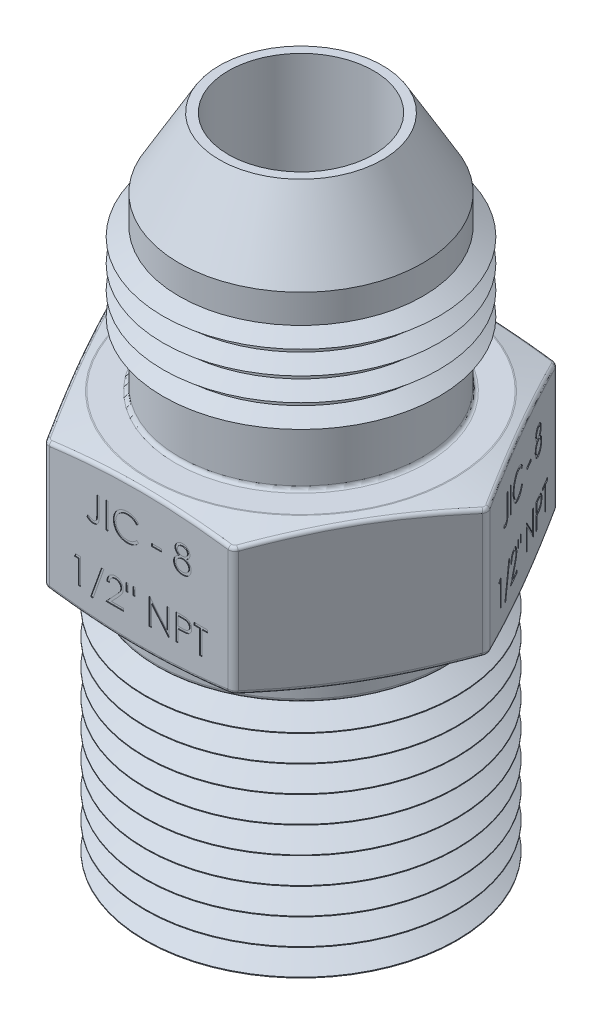
SolidWorks part; units mm, degrees
other "Fitting Body"
material "Plain Carbon Steel"
ref_plane "Front Plane" through (0, 0, 0) normal (0, 0, 1) x (1, 0, 0)
ref_plane "Top Plane" through (0, 0, 0) normal (0, 1, 0) x (1, 0, 0)
ref_plane "Right Plane" through (0, 0, 0) normal (1, 0, 0) x (0, 0, -1)
sketch "Sketch1" plane through (0, 0, 0) normal (0, 1, 0) x (1, 0, 0)
  line L1 (12.8316, 0) -> (6.4158, 11.1125)
  line L2 (6.4158, 11.1125) -> (-6.4158, 11.1125)
  line L3 (-6.4158, 11.1125) -> (-12.8316, 0)
  line L4 (-12.8316, 0) -> (-6.4158, -11.1125)
  line L5 (-6.4158, -11.1125) -> (6.4158, -11.1125)
  line L6 (6.4158, -11.1125) -> (12.8316, 0)
  circle A0 centre (0, 0) radius 11.1125 construction
  dimension "D1" = 22.225
extrude "Boss-Extrude1" add sketch "Sketch1" along normal mid plane 9.906
sketch "Sketch2" plane through (0, 4.953, 0) normal (0, 1, 0) x (1, 0, 0)
  circle A0 centre (0, 0) radius 10.414
  dimension "D1" = 20.828
extrude "Cut-Extrude1" cut sketch "Sketch2" against normal blind 8.255 draft 75 flip side to cut
sketch "Sketch3" plane through (0, -4.953, 0) normal (0, -1, 0) x (1, 0, 0)
  circle A0 centre (0, 0) radius 10.414 construction
  circle A1 centre (0, 0) radius 10.414
extrude "Cut-Extrude2" cut sketch "Sketch3" against normal blind 8.255 draft 75 flip side to cut
fillet "Fillet1" radius 0.508 6 edges at (6.4158, 0, 11.1125) (-6.4158, 0, 11.1125) (-12.8316, 0, 0) (-6.4158, 0, -11.1125) (6.4158, 0, -11.1125) (12.8316, 0, 0)
fillet "Fillet2" radius 0.254 25 edges at (12.7485, -4.3274, 0.0679) (6.433, -4.3274, -11.0066) (-6.3155, -4.3274, -11.0744) (-12.7485, -4.3274, -0.0679) (-6.433, -4.3274, 11.0066) (6.3155, -4.3274, 11.0744) (-6.3155, 4.3274, 11.0744) (-12.7485, 4.3274, 0.0679) (-6.433, 4.3274, -11.0066) (6.3155, 4.3274, -11.0744) (12.7485, 4.3274, -0.0679) (6.433, 4.3274, 11.0066) (0, 4.953, 10.414)
sketch "Sketch8" plane through (0, 4.953, 0) normal (0, 1, 0) x (1, 0, 0)
  circle A0 centre (0, 0) radius 8.3439
  dimension "D1" = 16.6878
extrude "Boss-Extrude6" add sketch "Sketch8" along normal blind 16.51
fillet "Fillet3" radius 0.254 1 edges at (0, 4.953, 8.3439)
chamfer "Chamfer1" distance 4.7625 angle 30 1 edges at (0, 21.463, 8.3439) first distance on face at (0, 5.207, 8.3439)
sketch "Sketch12" plane through (0, 0, 0) normal (0, 0, 1) x (1, 0, 0)
  line L0 (0, 0) -> (0, 14.097) construction
  line L1 (0, 14.097) -> (0, 21.463) construction
  line L2 (5.5943, 21.463) -> (-5.5943, 21.463) construction
  line L3 (0, 14.097) -> (8.3439, 14.097) construction
  line L4 (8.3439, 5.207) -> (8.3439, 16.7005) construction
  line L5 (8.3439, 14.097) -> (9.4438, 14.097) construction
  line L6 (8.3439, 14.732) -> (8.3439, 13.462)
  line L7 (8.3439, 14.732) -> (9.4438, 14.097)
  line L8 (9.4438, 14.097) -> (8.3439, 13.462)
  dimension "D1" = 60
  dimension "D2" = 1.27
  dimension "D3" = 7.366
revolve "Revolve2" add sketch "Sketch12" angle 360 about L0
pattern_linear "LPattern2" count 4 spacing 1.5875 along (0, -1, 0) of "Revolve2"
sketch "Sketch4" plane through (0, -4.953, 0) normal (0, -1, 0) x (1, 0, 0)
  circle A0 centre (0, 0) radius 9.906
  dimension "D1" = 19.812
extrude "Boss-Extrude7" add sketch "Sketch4" along normal blind 2.032
sketch "Sketch13" plane through (0, -6.985, 0) normal (0, -1, 0) x (1, 0, 0)
  circle A0 centre (0, 0) radius 10.668
  dimension "D1" = 21.336
extrude "Boss-Extrude8" add sketch "Sketch13" along normal offset from surface (16.256 mm away) 44.704 up to face at (0, 21.463, 5.5943)
sketch "Sketch14" plane through (0, 0, 0) normal (0, 0, 1) x (1, 0, 0)
  line L0 (0, 0) -> (0, -23.241) construction
  line L1 (-10.668, -23.241) -> (10.668, -23.241) construction
  line L2 (0, -23.241) -> (9.144, -23.241) construction
  line L3 (9.144, -23.241) -> (10.7152, -23.241) construction
  line L4 (10.7152, -23.241) -> (12.5295, -23.241) construction
  line L5 (12.5295, -22.3339) -> (12.5295, -24.1481)
  line L6 (10.7152, -22.3339) -> (10.7152, -24.1481) construction
  line L7 (12.5295, -22.3339) -> (10.7152, -22.3339)
  line L8 (10.7152, -22.3339) -> (9.144, -23.241)
  line L9 (9.144, -23.241) -> (10.7152, -24.1481)
  line L10 (10.7152, -24.1481) -> (12.5295, -24.1481)
  dimension "D1" = 60
  dimension "D2" = 1.8143
  dimension "D3" = 9.144
revolve "Cut-Revolve1" cut sketch "Sketch14" angle 360 about L0
pattern_linear "LPattern3" count 10 spacing 1.8143 along (0, 1, 0) of "Cut-Revolve1"
sketch "Sketch15" plane through (0, -23.241, 0) normal (0, -1, 0) x (1, 0, 0)
  circle A0 centre (0, 0) radius 4.9784
  dimension "D1" = 9.9568
extrude "Cut-Extrude3" cut sketch "Sketch15" against normal up to surface (44.704 mm away) up to face at (0, 21.463, 5.5943)
fillet "Fillet4" radius 0.254 3 edges at (0, -6.4725, 9.906) (0, -4.953, 9.906) (0, -4.953, -10.414)
sketch "Sketch Part Specs Info" plane through (0, 0, 11.1125) normal (0, 0, 1) x (1, 0, 0)
  line L0 (0, 0) -> (0, -3.1086) construction
  line L1 (0, 0) -> (0, 1.1201) construction
  line L2 (-6.1225, -3.1086) -> (6.1225, -3.1086) construction
  line L3 (-6.1225, 1.1201) -> (6.1225, 1.1201) construction
  line L4 (-6.1225, 4.1403) -> (-6.1225, -4.1403) construction
  text T0 "JIC - 8\r\n" font "Century Gothic" height 1.778
  text T1 "1/2\" NPT" font "Century Gothic" height 1.778
extrude "Cut Part Specs" cut sketch "Sketch Part Specs Info" against normal blind 0.0508
pattern_circular "CirPattern1" count 3 over 360 of "Cut Part Specs"
chamfer "Chamfer2" distance 0.508 angle 45 1 edges at (0, -23.241, -4.9784)
